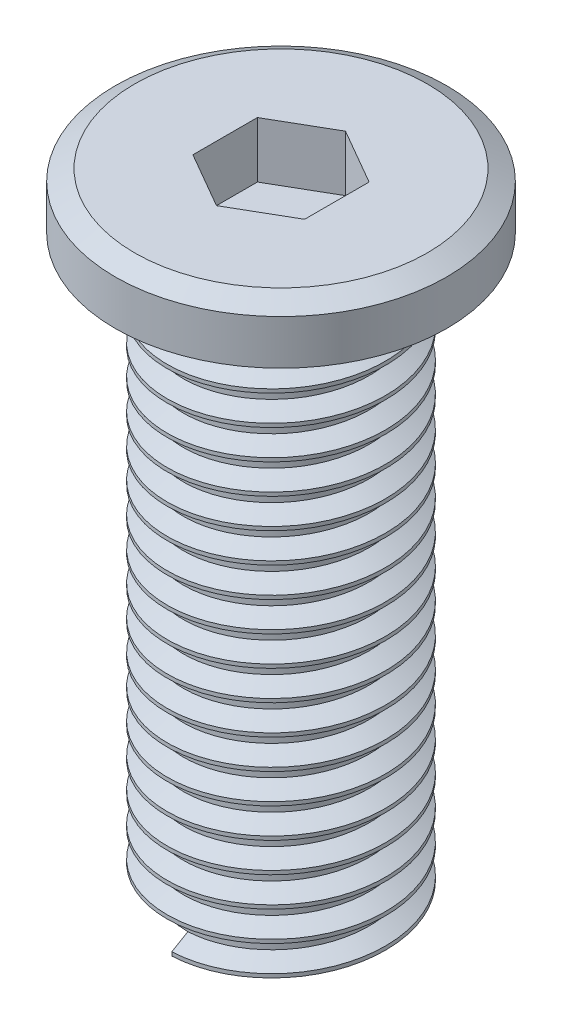
SolidWorks part; units mm, degrees
ref_plane "Front Plane" through (0, 0, 0) normal (0, 0, 1) x (1, 0, 0)
ref_plane "Top Plane" through (0, 0, 0) normal (0, 1, 0) x (1, 0, 0)
ref_plane "Right Plane" through (0, 0, 0) normal (1, 0, 0) x (0, 0, -1)
sketch "Sketch1" plane through (0, 0, 0) normal (0, 1, 0) x (1, 0, 0)
  circle A0 centre (0, 0) radius 4.45
  dimension "D1" = 8.9
extrude "Boss-Extrude1" add sketch "Sketch1" along normal blind 1.5
chamfer "Chamfer2" distance 0.3 angle 60 1 edges at (0, 1.5, 4.45) first distance on face at (0, 1.5, 4.45)
sketch "Sketch8" plane through (0, 1.5, 0) normal (0, 1, 0) x (1, 0, 0)
  line L1 (0, 1.7321) -> (-1.5, 0.866)
  line L2 (-1.5, 0.866) -> (-1.5, -0.866)
  line L3 (-1.5, -0.866) -> (0, -1.7321)
  line L4 (0, -1.7321) -> (1.5, -0.866)
  line L5 (1.5, -0.866) -> (1.5, 0.866)
  line L6 (1.5, 0.866) -> (0, 1.7321)
  circle A0 centre (0, 0) radius 1.5 construction
  dimension "D1" = 3
  dimension "D2" = 1.5
extrude "Cut-Extrude1" cut sketch "Sketch8" against normal blind 3
sketch "Sketch3" plane through (0, 0, 0) normal (0, -1, 0) x (1, 0, 0)
  circle A0 centre (0, 0) radius 2.5
  dimension "D1" = 5
extrude "Boss-Extrude2" add sketch "Sketch3" along normal blind 15
thread "Thread1" pitch 0.8 method extrude profile "Thread Profile2" start angle 0, offset 0, length 0, pitch 0.8, diameter 5
ref_plane "Plane2" through (-2.5, 0, 0) normal (0, 0, 1) x (-1, 0, 0)
sketch "Thread Profile2" plane through (-2.5, 0, 0) normal (0, 0, 1) x (-1, 0, 0)
  line L0 (0, 0) -> (0, 0.8) construction
  line L1 (0, 0) -> (0.433, 0.25)
  line L2 (0.433, 0.25) -> (0.433, 0.35)
  line L3 (0.433, 0.35) -> (0, 0.6)
  line L4 (0.433, 0.3) -> (0, 0.3) construction
  line L11 (0, 0) -> (0, 0.6)
  point P2 (0, 0)
  dimension "Pitch" = 0.8
  dimension "Profile_Angle" = 60
  dimension "Profile_Land" = 0.1
  dimension "Profile_Height" = 0.433
